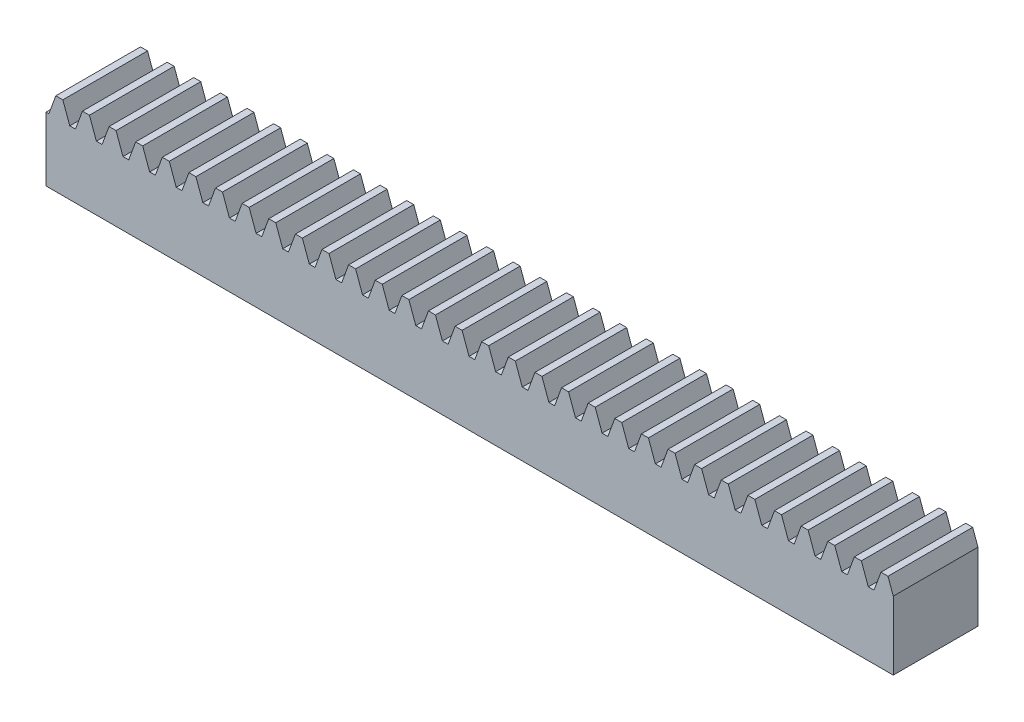
SolidWorks part; units mm, degrees
ref_plane "Front" through (0, 0, 0) normal (0, 0, 1) x (1, 0, 0)
ref_plane "Top" through (0, 0, 0) normal (0, 1, 0) x (1, 0, 0)
ref_plane "Right" through (0, 0, 0) normal (1, 0, 0) x (0, 0, -1)
sketch "Ritning 1" plane through (0, 0, 0) normal (0, 0, 1) x (1, 0, 0)
  line L1 (-124.1, -4.9) -> (125.9, -4.9)
  line L2 (-124.1, -4.9) -> (-124.1, 4.9)
  line L3 (-124.1, 4.9) -> (125.9, 4.9)
  line L4 (125.9, -4.9) -> (125.9, 4.9)
  dimension "D1" = 125.9
  dimension "D2" = 124.1
  dimension "D3" = 4.9
  dimension "D4" = 4.9
extrude "Kuggstångsämne" add sketch "Ritning 1" along normal blind 10
sketch "Ritning 2" plane through (0, 0, 10) normal (0, 0, 1) x (1, 0, 0)
  line L0 (-124.4383, 2.65) -> (-123.7617, 2.65)
  line L1 (-125.2572, 4.9) -> (-124.1, 6.0572)
  line L2 (125.9, -4.9) -> (125.9, 4.9) construction
  line L3 (-124.1, -4.9) -> (125.9, -4.9) construction
  line L7 (-124.1, 6.0572) -> (-122.9428, 4.9)
  line L9 (-122.9428, 4.9) -> (-123.7617, 2.65)
  spline S0 degree 3 poles (-125.2572, 4.9) (-124.9842, 4.15) (-124.7113, 3.4) (-124.4383, 2.65) knots 0 0 0 0 1 1 1 1
  dimension "D1" = 248.8428
  dimension "D2" = 249.6617
  dimension "D3" = 250
  dimension "D4" = 250.3383
  dimension "D5" = 7.55
  dimension "D6" = 9.8
extrude "Kugglucka" cut sketch "Ritning 2" against normal blind 10
ref_axis "Axis" through (125.9, 4.9, 10) along (-1, 0, 0)
pattern_linear "LPattern" count 80 spacing 3.1416 along (1, 0, 0) of "Kugglucka"
sketch "Sketch1" plane through (0, 0, 10) normal (0, 0, 1) x (1, 0, 0)
  line L1 (-124.1, -4.9) -> (125.9, -4.9) construction
  line L2 (-24.1, -4.9) -> (-24.1, 34.4047)
  line L5 (-24.1, 34.4047) -> (165.0559, 34.4047)
  line L6 (165.0559, 34.4047) -> (170.1232, -36.8051)
  line L7 (170.1232, -36.8051) -> (-46.9732, -44.8062)
  line L8 (-46.9732, -44.8062) -> (-24.1, -4.9)
extrude "Cut-Extrude1" cut sketch "Sketch1" against normal blind 10
